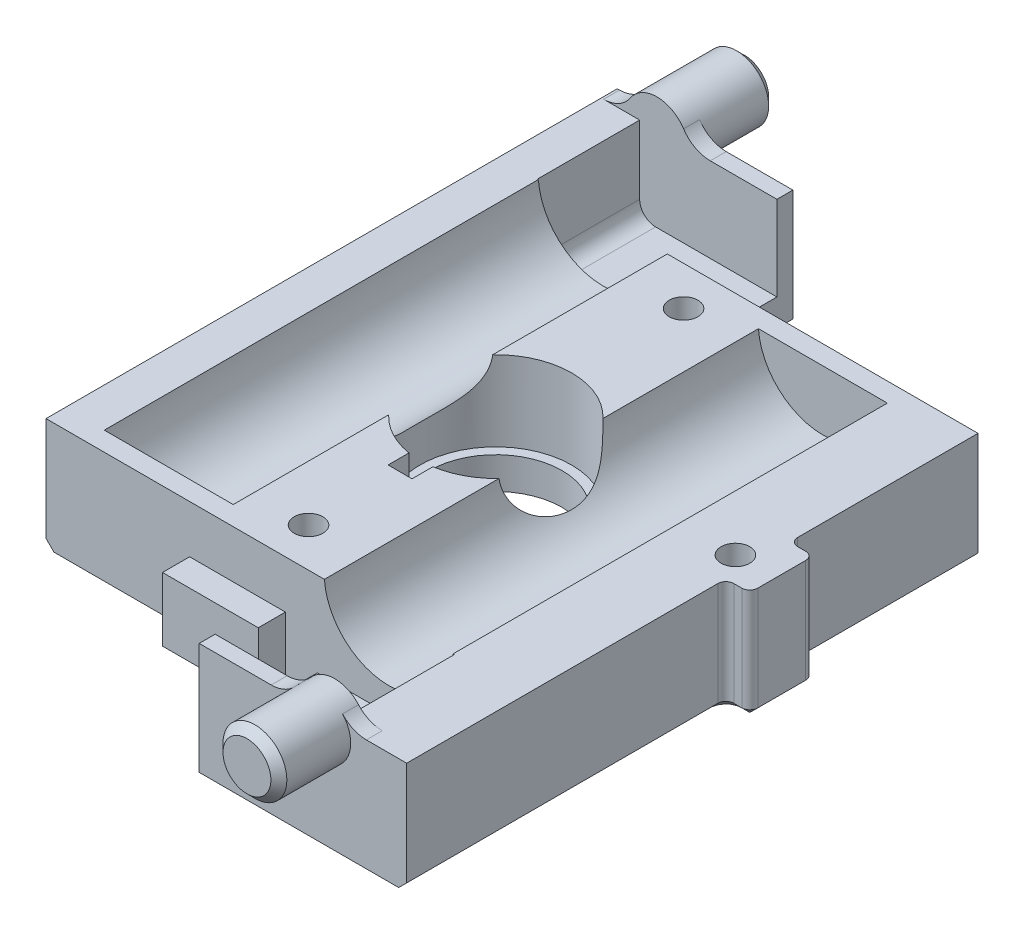
SolidWorks part; units mm, degrees
ref_plane "Front Plane" through (0, 0, 0) normal (0, 0, 1) x (1, 0, 0)
ref_plane "Top Plane" through (0, 0, 0) normal (0, 1, 0) x (1, 0, 0)
ref_plane "Right Plane" through (0, 0, 0) normal (1, 0, 0) x (0, 0, -1)
sketch "Sketch1" plane through (0, 0, 0) normal (0, 1, 0) x (1, 0, 0)
  line L1 (-61.4569, -66.3705) -> (-31.4569, -66.3705)
  line L2 (-61.4569, -66.3705) -> (-61.4569, -35.5705)
  line L3 (-61.4569, -35.5705) -> (-31.4569, -35.5705)
  line L4 (-31.4569, -66.3705) -> (-31.4569, -35.5705)
  dimension "D1" = 30.8
  dimension "D2" = 30
extrude "Boss-Extrude1" add sketch "Sketch1" along normal blind 7
sketch "Sketch2" plane through (0, 0, 0) normal (0, -1, 0) x (1, 0, 0)
  circle A0 centre (-47.4719, 50.9705) radius 4.15
  dimension "D1" = 8.3
extrude "Cut-Extrude1" cut sketch "Sketch2" against normal blind 6.5
sketch "Sketch3" plane through (0, 0, 0) normal (0, -1, 0) x (1, 0, 0)
  line L1 (-31.4569, 66.3705) -> (-46.4569, 66.3705)
  line L2 (-31.4569, 66.3705) -> (-31.4569, 65.1705)
  line L3 (-31.4569, 65.1705) -> (-46.4569, 65.1705)
  line L4 (-46.4569, 66.3705) -> (-46.4569, 65.1705)
  line L5 (-61.4569, 66.3705) -> (-52.4569, 66.3705)
  line L6 (-61.4569, 66.3705) -> (-61.4569, 65.1705)
  line L7 (-61.4569, 65.1705) -> (-52.4569, 65.1705)
  line L8 (-52.4569, 66.3705) -> (-52.4569, 65.1705)
  line L9 (-31.4569, 35.5705) -> (-42.4569, 35.5705)
  line L10 (-31.4569, 35.5705) -> (-31.4569, 36.7705)
  line L11 (-31.4569, 36.7705) -> (-42.4569, 36.7705)
  line L12 (-42.4569, 35.5705) -> (-42.4569, 36.7705)
  line L13 (-61.4569, 35.5705) -> (-48.4569, 35.5705)
  line L14 (-61.4569, 35.5705) -> (-61.4569, 36.7705)
  line L15 (-61.4569, 36.7705) -> (-48.4569, 36.7705)
  line L16 (-48.4569, 35.5705) -> (-48.4569, 36.7705)
  dimension "D1" = 15
  dimension "D2" = 9
  dimension "D3" = 1.2
  dimension "D4" = 1.2
  dimension "D5" = 1.2
  dimension "D6" = 1.2
  dimension "D7" = 11
  dimension "D8" = 13
extrude "Cut-Extrude2" cut sketch "Sketch3" against normal blind 4
sketch "Sketch4" plane through (0, 0, 66.3705) normal (0, 0, 1) x (1, 0, 0)
  line L1 (-61.4569, 7) -> (-31.4569, 7)
  line L2 (-61.4569, 7) -> (-61.4569, 4)
  line L3 (-61.4569, 4) -> (-31.4569, 4)
  line L4 (-31.4569, 7) -> (-31.4569, 4)
extrude "Cut-Extrude3" cut sketch "Sketch4" against normal blind 1.2
sketch "Sketch5" plane through (0, 0, 35.5705) normal (0, 0, -1) x (-1, 0, 0)
  line L1 (61.4569, 4) -> (31.4569, 4)
  line L2 (61.4569, 4) -> (61.4569, 7)
  line L3 (61.4569, 7) -> (31.4569, 7)
  line L4 (31.4569, 4) -> (31.4569, 7)
extrude "Cut-Extrude4" cut sketch "Sketch5" against normal blind 1.2
sketch "Sketch6" plane through (0, 0, 65.1705) normal (0, 0, 1) x (1, 0, 0)
  line L0 (-44.0746, 7.3) -> (-35.8746, 7.3) construction
  circle A0 centre (-39.9746, 7.3) radius 4.05
  dimension "D1" = 8.1
extrude "Cut-Extrude5" cut sketch "Sketch6" against normal blind 27.2
sketch "Sketch7" plane through (0, 0, 36.7705) normal (0, 0, -1) x (-1, 0, 0)
  line L0 (50.8646, 7.3) -> (59.0646, 7.3) construction
  circle A0 centre (54.9646, 7.3) radius 4.05
  dimension "D1" = 8.1
extrude "Cut-Extrude6" cut sketch "Sketch7" against normal blind 27.2
sketch "Sketch8" plane through (0, 7, 0) normal (0, 1, 0) x (1, 0, 0)
  circle A0 centre (-47.4719, -50.9705) radius 4.75
  dimension "D1" = 9.5
extrude "Cut-Extrude7" cut sketch "Sketch8" against normal blind 5
sketch "Sketch10" plane through (0, 0, 65.1705) normal (0, 0, 1) x (1, 0, 0)
  line L5 (-31.4569, 0) -> (-31.4569, 7)
  line L6 (-31.4569, 7) -> (-35.8569, 7)
  line L7 (-31.4569, 7) -> (-35.9357, 7) construction
  line L8 (-35.8569, 7) -> (-35.8569, 1.7)
  line L9 (-35.8569, 1.7) -> (-44.4569, 1.7)
  line L10 (-44.4569, 1.7) -> (-44.4569, 0)
  line L11 (-46.4569, 0) -> (-31.4569, 0) construction
  line L12 (-44.4569, 0) -> (-31.4569, 0)
  dimension "D1" = 4.4
  dimension "D2" = 1.7
  dimension "D3" = 13
extrude "Boss-Extrude2" add sketch "Sketch10" along normal blind 6.4
fillet "Fillet1" radius 1 1 edges at (-35.8569, 1.7, 68.3705)
sketch "Sketch11" plane through (0, 0, 36.7705) normal (0, 0, -1) x (-1, 0, 0)
  line L0 (61.4569, 7) -> (61.4569, 0)
  line L1 (61.4569, 0) -> (50.4569, 0)
  line L2 (48.4569, 0) -> (61.4569, 0) construction
  line L3 (50.4569, 0) -> (50.4569, 1.7)
  line L4 (50.4569, 1.7) -> (59.0569, 1.7)
  line L5 (59.0569, 1.7) -> (59.0569, 7)
  line L6 (61.4569, 7) -> (59.0034, 7) construction
  line L7 (59.0569, 7) -> (61.4569, 7)
  dimension "D1" = 2.4
  dimension "D2" = 1.7
  dimension "D3" = 11
extrude "Boss-Extrude3" add sketch "Sketch11" along normal blind 6.4
fillet "Fillet2" radius 1 1 edges at (-59.0569, 1.7, 33.5705)
sketch "Sketch12" plane through (0, 7, 0) normal (0, 1, 0) x (1, 0, 0)
  line L1 (-46.7219, -56.9705) -> (-48.2219, -56.9705)
  line L2 (-46.7219, -56.9705) -> (-46.7219, -55.6264)
  line L3 (-46.7219, -55.6264) -> (-48.2219, -55.6264)
  line L4 (-48.2219, -56.9705) -> (-48.2219, -55.6264)
  arc A0 (-46.9719, -55.5935) -> (-47.9719, -55.5935) centre (-47.4719, -50.9705) ccw construction
  dimension "D1" = 1.5
  dimension "D2" = 0.75
  dimension "D3" = 6
extrude "Cut-Extrude8" cut sketch "Sketch12" against normal up to surface (5 mm away) up to face at (-47.4719, 2, 55.7205)
sketch "Sketch13" plane through (0, 0, 71.5705) normal (0, 0, 1) x (1, 0, 0)
  line L0 (-44.0134, 7) -> (-61.4569, 7) construction
  line L1 (-31.4569, 0) -> (-44.4569, 0)
  line L2 (-31.4569, 0) -> (-31.4569, 7)
  line L3 (-31.4569, 7) -> (-44.4569, 7)
  line L4 (-44.4569, 0) -> (-44.4569, 7)
extrude "Boss-Extrude4" add sketch "Sketch13" along normal blind 1
sketch "Sketch14" plane through (0, 0, 30.3705) normal (0, 0, -1) x (-1, 0, 0)
  line L0 (50.9257, 7) -> (31.4569, 7) construction
  line L1 (61.4569, 0) -> (50.4569, 0)
  line L2 (61.4569, 0) -> (61.4569, 7)
  line L3 (61.4569, 7) -> (50.4569, 7)
  line L4 (50.4569, 0) -> (50.4569, 7)
extrude "Boss-Extrude5" add sketch "Sketch14" along normal blind 1
sketch "Sketch15" plane through (0, 0, 71.5705) normal (0, 0, 1) x (1, 0, 0)
  circle A0 centre (-36.9646, 6.3322) radius 2
  dimension "D1" = 4
sketch "Sketch16" plane through (0, 0, 30.3705) normal (0, 0, -1) x (-1, 0, 0)
  circle A0 centre (57.9746, 6.8) radius 2
  dimension "D1" = 4
extrude "Boss-Extrude8" add sketch "Sketch15" along normal blind 5.5
extrude "Boss-Extrude9" add sketch "Sketch16" along normal blind 5.5
fillet "Fillet3" radius 2 1 edges at (-59.9645, 7, 29.8705)
fillet "Fillet4" radius 2 1 edges at (-55.9846, 7, 29.8705)
fillet "Fillet5" radius 2 2 edges at (-35.0793, 7, 72.0705) (-38.8498, 7, 72.0705)
chamfer "Chamfer2" distance 0.5 angle 45 1 edges at (-34.9646, 6.3322, 77.0705)
chamfer "Chamfer3" distance 0.5 angle 45 1 edges at (-59.9746, 6.8, 24.8705)
sketch "Sketch17" plane through (-31.4569, 0, 0) normal (1, 0, 0) x (0, 0, -1)
  line L0 (-72.5705, 7) -> (-36.7705, 7) construction
  line L1 (-52.5705, 7) -> (-48.5705, 7)
  line L2 (-52.5705, 7) -> (-52.5705, 0)
  line L3 (-52.5705, 0) -> (-48.5705, 0)
  line L4 (-48.5705, 7) -> (-48.5705, 0)
  line L5 (-72.5705, 0) -> (-36.7705, 0) construction
  line L6 (-36.7705, 7) -> (-36.7705, 0) construction
  dimension "D1" = 4
  dimension "D2" = 11.8
extrude "Boss-Extrude10" add sketch "Sketch17" along normal blind 1.5
fillet "Fillet7" radius 0.5 4 edges at (-31.4569, 3.5, 52.5705) (-29.9569, 3.5, 52.5705) (-29.9569, 3.5, 48.5705) (-31.4569, 3.5, 48.5705)
sketch "Sketch18" plane through (0, 0, 0) normal (0, -1, 0) x (1, 0, 0)
  circle A0 centre (-32.4569, 50.9705) radius 0.9
  dimension "D1" = 1.8
extrude "Cut-Extrude9" cut sketch "Sketch18" against normal through all
sketch "Sketch19" plane through (0, 0, 0) normal (0, -1, 0) x (1, 0, 0)
  circle A0 centre (-32.4569, 50.9705) radius 1.6
  dimension "D1" = 3.2
extrude "Cut-Extrude10" cut sketch "Sketch19" against normal blind 2
sketch "Sketch20" plane through (0, 0, 0) normal (0, -1, 0) x (1, 0, 0)
  circle A0 centre (-47.4569, 62.7205) radius 0.9
  circle A1 centre (-47.4569, 39.2205) radius 0.9
  dimension "D1" = 1.8
  dimension "D2" = 1.8
extrude "Cut-Extrude11" cut sketch "Sketch20" against normal through all
sketch "Sketch21" plane through (0, 0, 0) normal (0, -1, 0) x (1, 0, 0)
  circle A0 centre (-47.4569, 62.7205) radius 1.6
  circle A1 centre (-47.4569, 39.2205) radius 1.6
  dimension "D1" = 3.2
  dimension "D2" = 3.2
extrude "Cut-Extrude12" cut sketch "Sketch21" against normal blind 2
chamfer "Chamfer6" distance 0.5 angle 45 9 edges at (-61.4569, 0, 47.2705) (-31.3104, 0, 48.4241) (-30.7069, 0, 48.5705) (-30.1033, 0, 48.717) (-29.9569, 0, 50.5705) (-30.1033, 0, 52.4241) (-30.7069, 0, 52.5705) (-31.3104, 0, 52.717) (-31.4569, 0, 62.8205)
sketch "Sketch22" plane through (0, 0, 35.5705) normal (0, 0, -1) x (-1, 0, 0)
  line L1 (42.4569, 4) -> (48.4569, 4)
  line L2 (42.4569, 4) -> (42.4569, 0)
  line L3 (42.4569, 0) -> (48.4569, 0)
  line L4 (48.4569, 4) -> (48.4569, 0)
extrude "Boss-Extrude11" add sketch "Sketch22" along normal blind 0.5
sketch "Sketch23" plane through (0, 0, 66.3705) normal (0, 0, 1) x (1, 0, 0)
  line L1 (-52.4569, 4) -> (-46.4569, 4)
  line L2 (-52.4569, 4) -> (-52.4569, 0)
  line L3 (-52.4569, 0) -> (-46.4569, 0)
  line L4 (-46.4569, 4) -> (-46.4569, 0)
extrude "Boss-Extrude12" add sketch "Sketch23" along normal blind 0.5
